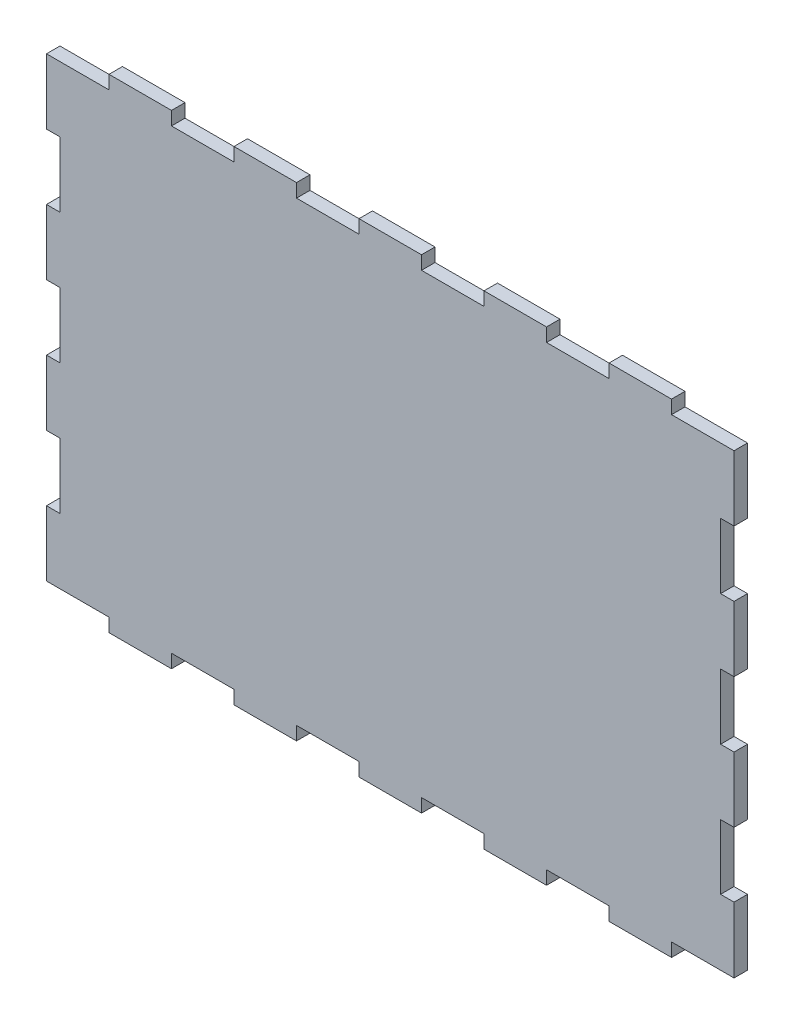
SolidWorks part; units mm, degrees
ref_plane "Alzado" through (0, 0, 0) normal (0, 0, 1) x (1, 0, 0)
ref_plane "Planta" through (0, 0, 0) normal (0, 1, 0) x (1, 0, 0)
ref_plane "Vista lateral" through (0, 0, 0) normal (1, 0, 0) x (0, 0, -1)
sketch "Croquis1" plane through (0, 0, 0) normal (0, 0, 1) x (1, 0, 0)
  line L0 (0, -17.0016) -> (0, -14.0016)
  line L1 (-48.39, -14.0016) -> (0, -14.0016) construction
  line L2 (0, -17.0016) -> (104.61, -17.0016)
  line L3 (101.61, -17.0016) -> (101.61, -49.332) construction
  line L4 (-227.956, -78.0016) -> (93.758, -78.0016) construction
  line L5 (-48.39, -14.0016) -> (-48.39, -78.0016) construction
  line L6 (78.6222, -39.0016) -> (-38.712, -39.0016) construction
  line L7 (0, -14.0016) -> (0, -17.0016) construction
  line L8 (0, -17.0016) -> (-48.39, -17.0016) construction
  line L9 (-48.39, -14.0016) -> (-38.712, -14.0016)
  line L10 (-38.712, -14.0016) -> (-38.712, -17.0016)
  line L11 (-38.712, -17.0016) -> (-29.034, -17.0016)
  line L12 (-29.034, -17.0016) -> (-29.034, -14.0016)
  line L13 (-29.034, -14.0016) -> (-19.356, -14.0016)
  line L14 (-19.356, -14.0016) -> (-19.356, -17.0016)
  line L15 (-19.356, -17.0016) -> (-9.678, -17.0016)
  line L16 (-9.678, -17.0016) -> (-9.678, -14.0016)
  line L17 (-9.678, -14.0016) -> (0, -14.0016)
  line L18 (104.61, -17.0016) -> (104.61, -78.0016) construction
  line L19 (104.61, -17.0016) -> (104.61, -29.2016)
  line L20 (104.61, -29.2016) -> (101.61, -29.2016)
  line L21 (101.61, -29.2016) -> (101.61, -41.4016)
  line L22 (101.61, -41.4016) -> (104.61, -41.4016)
  line L23 (104.61, -41.4016) -> (104.61, -53.6016)
  line L24 (104.61, -53.6016) -> (101.61, -53.6016)
  line L25 (101.61, -53.6016) -> (101.61, -65.8016)
  line L26 (101.61, -65.8016) -> (104.61, -65.8016)
  line L27 (104.61, -65.8016) -> (104.61, -78.0016)
  line L28 (-45.39, -56.5563) -> (-45.39, 45.6638) construction
  line L29 (-48.39, -14.0016) -> (-48.39, -26.8016)
  line L30 (-48.39, -26.8016) -> (-45.39, -26.8016)
  line L31 (-45.39, -26.8016) -> (-45.39, -39.6016)
  line L32 (-45.39, -39.6016) -> (-48.39, -39.6016)
  line L33 (-48.39, -39.6016) -> (-48.39, -52.4016)
  line L34 (-48.39, -52.4016) -> (-45.39, -52.4016)
  line L35 (-45.39, -52.4016) -> (-45.39, -65.2016)
  line L36 (-45.39, -65.2016) -> (-48.39, -65.2016)
  line L37 (-48.39, -65.2016) -> (-48.39, -78.0016)
  line L38 (-102.5031, -75.0016) -> (75.9308, -75.0016) construction
  line L39 (-124.386, -156.1001) -> (179.1879, -156.1001) construction
  line L40 (-48.39, -153.1001) -> (104.61, -153.1001) construction
  line L41 (-48.39, -78.0016) -> (-34.4809, -78.0016)
  line L42 (-34.4809, -78.0016) -> (-34.4809, -75.0016)
  line L43 (-34.4809, -75.0016) -> (-20.5718, -75.0016)
  line L44 (-20.5718, -75.0016) -> (-20.5718, -78.0016)
  line L45 (-20.5718, -78.0016) -> (-6.6627, -78.0016)
  line L46 (-6.6627, -78.0016) -> (-6.6627, -75.0016)
  line L47 (-6.6627, -75.0016) -> (7.2464, -75.0016)
  line L48 (7.2464, -75.0016) -> (7.2464, -78.0016)
  line L49 (7.2464, -78.0016) -> (21.1555, -78.0016)
  line L50 (21.1555, -78.0016) -> (21.1555, -75.0016)
  line L51 (21.1555, -75.0016) -> (35.0645, -75.0016)
  line L52 (35.0645, -75.0016) -> (35.0645, -78.0016)
  line L53 (35.0645, -78.0016) -> (48.9736, -78.0016)
  line L54 (48.9736, -78.0016) -> (48.9736, -75.0016)
  line L55 (48.9736, -75.0016) -> (62.8827, -75.0016)
  line L56 (62.8827, -75.0016) -> (62.8827, -78.0016)
  line L57 (62.8827, -78.0016) -> (76.7918, -78.0016)
  line L58 (76.7918, -78.0016) -> (76.7918, -75.0016)
  line L59 (76.7918, -75.0016) -> (90.7009, -75.0016)
  line L60 (90.7009, -75.0016) -> (90.7009, -78.0016)
  line L61 (90.7009, -78.0016) -> (104.61, -78.0016)
  line L62 (-48.39, -153.1001) -> (-48.39, -260.7101) construction
  line L63 (-48.39, -260.7101) -> (104.61, -260.7101) construction
  line L64 (104.61, -153.1001) -> (104.61, -260.7101) construction
  line L65 (-68.7634, -257.7101) -> (144.8732, -257.7101) construction
  line L66 (101.61, -78.0016) -> (101.61, -269.1968) construction
  line L67 (-45.39, -153.1001) -> (-45.39, -251.8965) construction
  line L68 (-34.4809, -78.0016) -> (-34.4809, -243.0877) construction
  line L69 (-20.5718, -78.0016) -> (-20.5718, -243.0877) construction
  line L70 (-6.6627, -75.0016) -> (-6.6627, -243.0877) construction
  line L71 (7.2464, -75.0016) -> (7.2464, -243.0877) construction
  line L72 (21.1555, -75.0016) -> (21.1555, -243.0877) construction
  line L73 (35.0645, -75.0016) -> (35.0645, -243.0877) construction
  line L74 (48.9736, -75.0016) -> (48.9736, -243.0877) construction
  line L75 (62.8827, -75.0016) -> (62.8827, -243.0877) construction
  line L76 (76.7918, -75.0016) -> (76.7918, -243.0877) construction
  line L77 (90.7009, -75.0016) -> (90.7009, -243.0877) construction
  line L78 (-34.4809, -156.1001) -> (-48.39, -156.1001)
  line L79 (-34.4809, -156.1001) -> (-34.4809, -153.1001)
  line L80 (-34.4809, -153.1001) -> (-20.5718, -153.1001)
  line L81 (-20.5718, -153.1001) -> (-20.5718, -156.1001)
  line L82 (-20.5718, -156.1001) -> (-6.6627, -156.1001)
  line L83 (-6.6627, -156.1001) -> (-6.6627, -153.1001)
  line L84 (-6.6627, -153.1001) -> (7.2464, -153.1001)
  line L85 (7.2464, -153.1001) -> (7.2464, -156.1001)
  line L86 (7.2464, -156.1001) -> (21.1555, -156.1001)
  line L87 (21.1555, -156.1001) -> (21.1555, -153.1001)
  line L88 (21.1555, -153.1001) -> (35.0645, -153.1001)
  line L89 (35.0645, -153.1001) -> (35.0645, -156.1001)
  line L90 (35.0645, -156.1001) -> (48.9736, -156.1001)
  line L91 (48.9736, -156.1001) -> (48.9736, -153.1001)
  line L92 (48.9736, -153.1001) -> (62.8827, -153.1001)
  line L93 (62.8827, -153.1001) -> (62.8827, -156.1001)
  line L94 (62.8827, -156.1001) -> (76.7918, -156.1001)
  line L95 (76.7918, -156.1001) -> (76.7918, -153.1001)
  line L96 (76.7918, -153.1001) -> (90.7009, -153.1001)
  line L97 (90.7009, -153.1001) -> (90.7009, -156.1001)
  line L98 (90.7009, -156.1001) -> (104.61, -156.1001)
  line L99 (-48.39, -257.7101) -> (-34.4809, -257.7101)
  line L100 (-34.4809, -257.7101) -> (-34.4809, -260.7101)
  line L101 (-34.4809, -260.7101) -> (-20.5718, -260.7101)
  line L102 (-20.5718, -260.7101) -> (-20.5718, -257.7101)
  line L103 (-20.5718, -257.7101) -> (-6.6627, -257.7101)
  line L104 (-6.6627, -257.7101) -> (-6.6627, -260.7101)
  line L105 (-6.6627, -260.7101) -> (7.2464, -260.7101)
  line L106 (7.2464, -260.7101) -> (7.2464, -257.7101)
  line L107 (7.2464, -257.7101) -> (21.1555, -257.7101)
  line L108 (21.1555, -257.7101) -> (21.1555, -260.7101)
  line L109 (21.1555, -260.7101) -> (35.0645, -260.7101)
  line L110 (35.0645, -260.7101) -> (35.0645, -257.7101)
  line L111 (35.0645, -257.7101) -> (48.9736, -257.7101)
  line L112 (48.9736, -257.7101) -> (48.9736, -260.7101)
  line L113 (48.9736, -260.7101) -> (62.8827, -260.7101)
  line L114 (62.8827, -260.7101) -> (62.8827, -257.7101)
  line L115 (62.8827, -257.7101) -> (76.7918, -257.7101)
  line L116 (76.7918, -257.7101) -> (76.7918, -260.7101)
  line L117 (76.7918, -260.7101) -> (90.7009, -260.7101)
  line L118 (90.7009, -260.7101) -> (90.7009, -257.7101)
  line L119 (90.7009, -257.7101) -> (104.61, -257.7101)
  line L120 (-226.2526, -14.0016) -> (-226.2526, -78.0016) construction
  line L121 (-290.2526, -78.0016) -> (-226.2526, -78.0016) construction
  line L122 (-226.2526, -78.0016) -> (-226.2526, -287.7111) construction
  line L123 (-290.2526, -78.0016) -> (-290.2526, -287.7111) construction
  line L124 (-290.2526, -287.7111) -> (-226.2526, -287.7111) construction
  line L125 (-48.39, -26.8016) -> (-105.5506, -26.8016) construction
  line L126 (-48.39, -39.6016) -> (-94.7516, -39.6016) construction
  line L127 (-48.39, -52.4016) -> (-71.8061, -52.4016) construction
  line L128 (-48.39, -65.2016) -> (-67.7461, -65.2016) construction
  line L129 (-277.4526, -73.8444) -> (-277.4526, -111.8004) construction
  line L130 (-264.6526, -73.8444) -> (-264.6526, -111.8004) construction
  line L131 (-251.8526, -90.832) -> (-251.8526, -128.788) construction
  line L132 (-239.0526, -73.8444) -> (-239.0526, -111.8004) construction
  line L133 (-229.2526, -73.8444) -> (-229.2526, -93.389) construction
  line L134 (165.3571, -156.1001) -> (174.5571, -156.1001)
  line L135 (174.5571, -156.1001) -> (174.5571, -153.1001)
  line L136 (174.5571, -153.1001) -> (186.7571, -153.1001)
  line L137 (186.7571, -153.1001) -> (186.7571, -156.1001)
  line L138 (186.7571, -156.1001) -> (198.9571, -156.1001)
  line L139 (198.9571, -156.1001) -> (198.9571, -153.1001)
  line L140 (198.9571, -153.1001) -> (211.1571, -153.1001)
  line L141 (211.1571, -153.1001) -> (211.1571, -156.1001)
  line L142 (211.1571, -156.1001) -> (223.3571, -156.1001)
  line L143 (-229.2526, -156.1001) -> (-229.2526, -170.6158)
  line L144 (-229.2526, -170.6158) -> (-226.2526, -170.6158)
  line L145 (-226.2526, -170.6158) -> (-226.2526, -185.1315)
  line L146 (-226.2526, -185.1315) -> (-229.2526, -185.1315)
  line L147 (-229.2526, -185.1315) -> (-229.2526, -199.6473)
  line L148 (-229.2526, -199.6473) -> (-226.2526, -199.6473)
  line L149 (-226.2526, -199.6473) -> (-226.2526, -220.163)
  line L150 (-226.2526, -220.163) -> (-229.2526, -220.163)
  line L151 (-48.39, -257.7101) -> (-48.39, -243.1944)
  line L152 (-48.39, -243.1944) -> (-45.39, -243.1944)
  line L153 (-45.39, -243.1944) -> (-45.39, -228.6787)
  line L154 (-45.39, -228.6787) -> (-48.39, -228.6787)
  line L155 (-48.39, -228.6787) -> (-48.39, -214.163)
  line L156 (-48.39, -214.163) -> (-45.39, -214.163)
  line L157 (-45.39, -214.163) -> (-45.39, -199.6473)
  line L158 (-45.39, -199.6473) -> (-48.39, -199.6473)
  line L159 (-48.39, -199.6473) -> (-48.39, -185.1315)
  line L160 (-48.39, -185.1315) -> (-45.39, -185.1315)
  line L161 (-45.39, -185.1315) -> (-45.39, -170.6158)
  line L162 (-45.39, -170.6158) -> (-48.39, -170.6158)
  line L163 (-48.39, -170.6158) -> (-48.39, -156.1001)
  line L164 (-48.39, -228.6787) -> (-80.3979, -228.6787) construction
  line L165 (-48.39, -243.1944) -> (-76.899, -243.1944) construction
  line L166 (-48.39, -214.163) -> (-74.7996, -214.163) construction
  line L167 (-48.39, -199.6473) -> (-74.7996, -199.6473) construction
  line L168 (-74.7996, -185.1315) -> (-48.39, -185.1315) construction
  line L169 (-48.39, -170.6158) -> (-71.0675, -170.6158) construction
  line L170 (-229.2526, -220.163) -> (-229.2526, -234.6787)
  line L171 (-287.2526, -73.8444) -> (-287.2526, -109.848) construction
  line L172 (-229.2526, -234.6787) -> (-226.2526, -234.6787)
  line L173 (-226.2526, -234.6787) -> (-226.2526, -249.1944)
  line L174 (-226.2526, -249.1944) -> (-229.2526, -249.1944)
  line L175 (-229.2526, -249.1944) -> (-229.2526, -257.7101)
  line L176 (223.3571, -257.7101) -> (211.1571, -257.7101)
  line L177 (211.1571, -257.7101) -> (211.1571, -260.7101)
  line L178 (211.1571, -260.7101) -> (198.9571, -260.7101)
  line L179 (198.9571, -260.7101) -> (198.9571, -257.7101)
  line L180 (198.9571, -257.7101) -> (186.7571, -257.7101)
  line L181 (186.7571, -257.7101) -> (186.7571, -260.7101)
  line L182 (186.7571, -260.7101) -> (174.5571, -260.7101)
  line L183 (174.5571, -260.7101) -> (174.5571, -257.7101)
  line L184 (-287.2526, -257.7101) -> (-287.2526, -243.1944)
  line L185 (-287.2526, -243.1944) -> (-290.2526, -243.1944)
  line L186 (-290.2526, -243.1944) -> (-290.2526, -228.6787)
  line L187 (-290.2526, -228.6787) -> (-287.2526, -228.6787)
  line L188 (-287.2526, -228.6787) -> (-287.2526, -214.163)
  line L189 (-287.2526, -214.163) -> (-290.2526, -214.163)
  line L190 (-290.2526, -214.163) -> (-290.2526, -199.6473)
  line L191 (-290.2526, -199.6473) -> (-287.2526, -199.6473)
  line L192 (-287.2526, -199.6473) -> (-287.2526, -185.1315)
  line L193 (-287.2526, -185.1315) -> (-290.2526, -185.1315)
  line L194 (-290.2526, -185.1315) -> (-290.2526, -170.6158)
  line L195 (-290.2526, -170.6158) -> (-287.2526, -170.6158)
  line L196 (-287.2526, -170.6158) -> (-287.2526, -156.1001)
  line L197 (174.5571, -257.7101) -> (165.3571, -257.7101)
  line L198 (-315.487, -120.5373) -> (-315.487, -274.6014) construction
  line L199 (-423.097, -153.1001) -> (-423.097, -80.2802) construction
  line L200 (-420.097, -153.1001) -> (-420.097, -73.0846) construction
  line L201 (-405.5813, -153.1001) -> (-405.5813, -73.0846) construction
  line L202 (-391.0655, -153.1001) -> (-391.0655, -77.6291) construction
  line L203 (-376.5498, -153.1001) -> (-376.5498, -80.2802) construction
  line L204 (-362.0341, -153.1001) -> (-362.0341, -73.0846) construction
  line L205 (-347.5184, -153.1001) -> (-347.5184, -77.6291) construction
  line L206 (-333.0027, -153.1001) -> (-333.0027, -73.0846) construction
  line L207 (-318.487, -153.1001) -> (-318.487, -77.6291) construction
  line L208 (-48.39, -21.6772) -> (-48.39, 38.9813) construction
  line L209 (-38.712, -14.0016) -> (-38.712, 45.6638) construction
  line L210 (-29.034, -14.0016) -> (-29.034, 45.6638) construction
  line L211 (-19.356, -14.0016) -> (-19.356, 45.6638) construction
  line L212 (-9.678, -14.0016) -> (-9.678, 45.6638) construction
  line L213 (0, -14.0016) -> (0, 45.6638) construction
  line L214 (2.5149, 38.1832) -> (-48.39, 38.1832) construction
  line L215 (-48.39, 86.5732) -> (-80.1148, 86.5732) construction
  line L216 (-48.39, 76.8952) -> (-75.2531, 76.8952) construction
  line L217 (-48.39, 67.2172) -> (-75.2531, 67.2172) construction
  line L218 (-48.39, 57.5392) -> (-80.1148, 57.5392) construction
  line L219 (-48.39, 47.8612) -> (-84.9766, 47.8612) construction
  line L220 (-318.487, 38.1832) -> (-318.487, 47.8612)
  line L221 (-48.39, 38.1832) -> (-76.9441, 38.1832) construction
  line L222 (-318.487, 47.8612) -> (-315.487, 47.8612)
  line L223 (-315.487, 47.8612) -> (-315.487, 57.5392)
  line L224 (-315.487, 57.5392) -> (-318.487, 57.5392)
  line L225 (-318.487, 57.5392) -> (-318.487, 67.2172)
  line L226 (-318.487, 67.2172) -> (-315.487, 67.2172)
  line L227 (-315.487, 67.2172) -> (-315.487, 76.8952)
  line L228 (-315.487, 76.8952) -> (-318.487, 76.8952)
  line L229 (-318.487, 76.8952) -> (-318.487, 86.5732)
  line L230 (-318.487, 86.5732) -> (-420.097, 86.5732)
  line L231 (-420.097, 86.5732) -> (-420.097, 76.8952)
  line L232 (-420.097, 76.8952) -> (-423.097, 76.8952)
  line L233 (-423.097, 76.8952) -> (-423.097, 67.2172)
  line L234 (-423.097, 67.2172) -> (-420.097, 67.2172)
  line L235 (-420.097, 67.2172) -> (-420.097, 57.5392)
  line L236 (-420.097, 57.5392) -> (-423.097, 57.5392)
  line L237 (-423.097, 57.5392) -> (-423.097, 47.8612)
  line L238 (-423.097, 47.8612) -> (-420.097, 47.8612)
  line L239 (-420.097, 47.8612) -> (-420.097, 38.1832)
  line L240 (-48.39, 41.1832) -> (-83.9517, 41.1832) construction
  line L241 (-318.487, 38.1832) -> (-333.0027, 38.1832)
  line L242 (-333.0027, 38.1832) -> (-333.0027, 41.1832)
  line L243 (-333.0027, 41.1832) -> (-347.5184, 41.1832)
  line L244 (-347.5184, 41.1832) -> (-347.5184, 38.1832)
  line L245 (-347.5184, 38.1832) -> (-362.0341, 38.1832)
  line L246 (-362.0341, 38.1832) -> (-362.0341, 41.1832)
  line L247 (-362.0341, 41.1832) -> (-376.5498, 41.1832)
  line L248 (-376.5498, 41.1832) -> (-376.5498, 38.1832)
  line L249 (-376.5498, 38.1832) -> (-391.0655, 38.1832)
  line L250 (-391.0655, 38.1832) -> (-391.0655, 41.1832)
  line L251 (-391.0655, 41.1832) -> (-405.5813, 41.1832)
  line L252 (-405.5813, 41.1832) -> (-405.5813, 38.1832)
  line L253 (-405.5813, 38.1832) -> (-420.097, 38.1832)
  line L254 (162.3571, -15.1529) -> (162.3571, -104.9762) construction
  line L255 (104.61, -29.2016) -> (145.8916, -29.2016) construction
  line L256 (104.61, -41.4016) -> (145.8916, -41.4016) construction
  line L257 (104.61, -65.8016) -> (131.4417, -65.8016) construction
  line L258 (104.61, -53.6016) -> (126.5441, -53.6016) construction
  line L259 (165.3571, -73.8444) -> (165.3571, -106.8492) construction
  line L260 (174.5571, -73.8444) -> (174.5571, -108.8044) construction
  line L261 (186.7571, -73.8444) -> (186.7571, -108.8044) construction
  line L262 (198.9571, -73.8444) -> (198.9571, -108.8044) construction
  line L263 (211.1571, -73.8444) -> (211.1571, -106.8492) construction
  line L264 (223.3571, -73.8444) -> (223.3571, -108.8044) construction
  line L265 (104.61, -257.7101) -> (104.61, -243.0877)
  line L266 (104.61, -243.0877) -> (101.61, -243.0877)
  line L267 (101.61, -243.0877) -> (101.61, -228.6787)
  line L268 (101.61, -228.6787) -> (104.61, -228.6787)
  line L269 (104.61, -228.6787) -> (104.61, -214.163)
  line L270 (104.61, -214.163) -> (101.61, -214.163)
  line L271 (101.61, -214.163) -> (101.61, -199.6473)
  line L272 (101.61, -199.6473) -> (104.61, -199.6473)
  line L273 (104.61, -199.6473) -> (104.61, -185.1315)
  line L274 (104.61, -185.1315) -> (101.61, -185.1315)
  line L275 (101.61, -185.1315) -> (101.61, -170.6158)
  line L276 (101.61, -170.6158) -> (104.61, -170.6158)
  line L277 (104.61, -170.6158) -> (104.61, -156.1001)
  line L278 (-229.2526, -156.1001) -> (-239.0526, -156.1001)
  line L279 (-239.0526, -156.1001) -> (-239.0526, -153.1001)
  line L280 (-239.0526, -153.1001) -> (-251.8526, -153.1001)
  line L281 (-251.8526, -153.1001) -> (-251.8526, -156.1001)
  line L282 (-251.8526, -156.1001) -> (-264.6526, -156.1001)
  line L283 (-264.6526, -156.1001) -> (-264.6526, -153.1001)
  line L284 (-264.6526, -153.1001) -> (-277.4526, -153.1001)
  line L285 (-277.4526, -153.1001) -> (-277.4526, -156.1001)
  line L286 (-277.4526, -156.1001) -> (-287.2526, -156.1001)
  line L287 (223.3571, -156.1001) -> (223.3571, -257.7101)
  line L288 (-229.2526, -257.7101) -> (-239.0526, -257.7101)
  line L289 (-239.0526, -257.7101) -> (-239.0526, -260.7101)
  line L290 (-239.0526, -260.7101) -> (-251.8526, -260.7101)
  line L291 (-251.8526, -260.7101) -> (-251.8526, -257.7101)
  line L292 (-251.8526, -257.7101) -> (-264.6526, -257.7101)
  line L293 (-264.6526, -257.7101) -> (-264.6526, -260.7101)
  line L294 (-264.6526, -260.7101) -> (-277.4526, -260.7101)
  line L295 (-277.4526, -260.7101) -> (-277.4526, -257.7101)
  line L296 (-277.4526, -257.7101) -> (-287.2526, -257.7101)
  line L297 (165.3571, -257.7101) -> (165.3571, -243.1944)
  line L298 (165.3571, -243.1944) -> (162.3571, -243.1944)
  line L299 (162.3571, -243.1944) -> (162.3571, -228.6787)
  line L300 (162.3571, -228.6787) -> (165.3571, -228.6787)
  line L301 (165.3571, -228.6787) -> (165.3571, -214.163)
  line L302 (165.3571, -214.163) -> (162.3571, -214.163)
  line L303 (162.3571, -214.163) -> (162.3571, -199.6473)
  line L304 (162.3571, -199.6473) -> (165.3571, -199.6473)
  line L305 (165.3571, -199.6473) -> (165.3571, -185.1315)
  line L306 (165.3571, -185.1315) -> (162.3571, -185.1315)
  line L307 (162.3571, -185.1315) -> (162.3571, -170.6158)
  line L308 (162.3571, -170.6158) -> (165.3571, -170.6158)
  line L309 (165.3571, -170.6158) -> (165.3571, -156.1001)
  circle A0 centre (73.11, -39.0016) radius 1.25
  circle A1 centre (31.5, -39.0016) radius 1.25
  circle A2 centre (-28.49, -39.0016) radius 1.25
  arc A3 (-226.2526, -65.2016) -> (-239.0526, -78.0016) centre (-226.2526, -78.0016) ccw construction
  arc A4 (-226.2526, -52.4016) -> (-251.8526, -78.0016) centre (-226.2526, -78.0016) ccw construction
  arc A5 (-226.2526, -39.6016) -> (-264.6526, -78.0016) centre (-226.2526, -78.0016) ccw construction
  arc A6 (-226.2526, -26.8016) -> (-277.4526, -78.0016) centre (-226.2526, -78.0016) ccw construction
  arc A7 (-226.2526, -14.0016) -> (-290.2526, -78.0016) centre (-226.2526, -78.0016) ccw construction
  arc A8 (-226.2526, -75.0016) -> (-229.2526, -78.0016) centre (-226.2526, -78.0016) ccw construction
  arc A9 (-226.2526, -17.0016) -> (-287.2526, -78.0016) centre (-226.2526, -78.0016) ccw construction
  arc A10 (-315.487, -156.1001) -> (-318.487, -153.1001) centre (-315.487, -153.1001) cw construction
  arc A11 (-315.487, -170.6158) -> (-333.0027, -153.1001) centre (-315.487, -153.1001) cw construction
  arc A12 (-315.487, -185.1315) -> (-347.5184, -153.1001) centre (-315.487, -153.1001) cw construction
  arc A13 (-315.487, -199.6473) -> (-362.0341, -153.1001) centre (-315.487, -153.1001) cw construction
  arc A14 (-315.487, -214.163) -> (-376.5498, -153.1001) centre (-315.487, -153.1001) cw construction
  arc A15 (-315.487, -228.6787) -> (-391.0655, -153.1001) centre (-315.487, -153.1001) cw construction
  arc A16 (-315.487, -243.1944) -> (-405.5813, -153.1001) centre (-315.487, -153.1001) cw construction
  arc A17 (-315.487, -257.7101) -> (-420.097, -153.1001) centre (-315.487, -153.1001) cw construction
  arc A18 (-315.487, -260.7101) -> (-423.097, -153.1001) centre (-315.487, -153.1001) cw construction
  arc A19 (-45.39, 38.1832) -> (-48.39, 41.1832) centre (-48.39, 38.1832) ccw construction
  arc A20 (-38.712, 38.1832) -> (-48.39, 47.8612) centre (-48.39, 38.1832) ccw construction
  arc A21 (-29.034, 38.1832) -> (-48.39, 57.5392) centre (-48.39, 38.1832) ccw construction
  arc A22 (-19.356, 38.1832) -> (-48.39, 67.2172) centre (-48.39, 38.1832) ccw construction
  arc A23 (-9.678, 38.1832) -> (-48.39, 76.8952) centre (-48.39, 38.1832) ccw construction
  arc A24 (0, 38.1832) -> (-48.39, 86.5732) centre (-48.39, 38.1832) ccw construction
  arc A25 (162.3571, -75.0016) -> (165.3571, -78.0016) centre (162.3571, -78.0016) cw construction
  arc A26 (162.3571, -65.8016) -> (174.5571, -78.0016) centre (162.3571, -78.0016) cw construction
  arc A27 (162.3571, -53.6016) -> (186.7571, -78.0016) centre (162.3571, -78.0016) cw construction
  arc A28 (162.3571, -41.4016) -> (198.9571, -78.0016) centre (162.3571, -78.0016) cw construction
  arc A29 (162.3571, -29.2016) -> (211.1571, -78.0016) centre (162.3571, -78.0016) cw construction
  arc A30 (162.3571, -17.0016) -> (223.3571, -78.0016) centre (162.3571, -78.0016) cw construction
  text T0 "TOP\r\n"
  dimension "D2" = 2.5
  dimension "D3" = 2.5
  dimension "D4" = 2.5
  dimension "D7" = 101.6
  dimension "D20" = 22
  dimension "D9" = 36
  dimension "D1" = 153
  dimension "D5" = 3
  dimension "D6" = 104.61
  dimension "D8" = 3
  dimension "D10" = 3
  dimension "D11" = 41.61
  dimension "D13" = 3
  dimension "D14" = 153
  dimension "D15" = 107.61
  dimension "D17" = 3
  dimension "D18" = 3
  dimension "D19" = 28.5
extrude "Saliente-Extruir1" add sketch "Croquis1" along normal blind 3 contours L276 L277 L98 L97 L96 L95 L94 L93 L92 L91 L90 L89 L88 L87 L86 L85 L84 L83 L82 L81 L80 L79 L78 L163 L162 L161 L160 L159 L158 L157 L156 L155 L154 L153 L152 L151 L99 L100 L101 L102 L103 L104 L105 L106 L107 L108 L109 L110 L111 L112 L113 region at (28.1115, -206.9059, 0)
